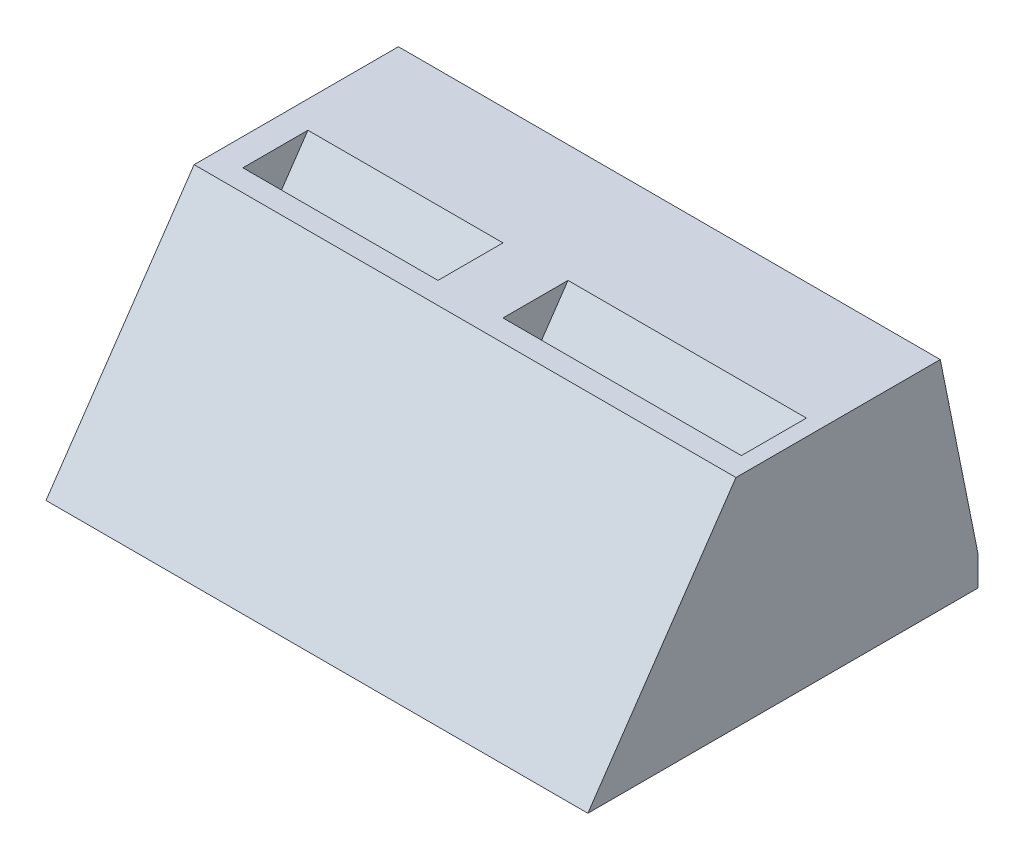
SolidWorks part; units mm, degrees
ref_plane "Ebene vorne" through (0, 0, 0) normal (0, 0, 1) x (1, 0, 0)
ref_plane "Ebene oben" through (0, 0, 0) normal (0, 1, 0) x (1, 0, 0)
ref_plane "Ebene rechts" through (0, 0, 0) normal (1, 0, 0) x (0, 0, -1)
sketch "Skizze1" plane through (0, 0, 0) normal (0, 0, 1) x (1, 0, 0)
  line L1 (-25, -15) -> (25, -15)
  line L2 (-25, -15) -> (-25, 15)
  line L3 (-25, 15) -> (25, 15)
  line L4 (25, -15) -> (25, 15)
  line L5 (-25, -15) -> (25, 15) construction
  line L6 (-25, 15) -> (25, -15) construction
  point P0 (0, 0)
  dimension "D1" = 50
  dimension "D2" = 30
extrude "Aufsatz-Linear austragen1" add sketch "Skizze1" along normal blind 40
ref_plane "Ebene1" through (0, 0, 0) normal (-1, 0, 0) x (0, 0, 1)
sketch "Skizze2" plane through (0, 0, 0) normal (-1, 0, 0) x (0, 0, 1)
  line L0 (7.5, 15) -> (28, -15)
  line L1 (40, 15) -> (0, 15) construction
  line L2 (40, -15) -> (0, -15) construction
  line L3 (28, -15) -> (34, -15)
  line L4 (34, -15) -> (13.5, 15)
  line L5 (13.5, 15) -> (7.5, 15)
  line L6 (40, 15) -> (40, -15) construction
  line L8 (26.6333, -13) -> (32.6333, -13)
  dimension "D1" = 6
  dimension "D2" = 6
  dimension "D3" = 7.5
  dimension "D4" = 2
extrude "FPV_Sender" cut sketch "Skizze2" against normal blind 22 from offset 1.5 contours L0 L8 L4 L5 region at (0, 1, 20.0667) offset against normal yes
sketch "Skizze4" plane through (0, 0, 0) normal (-1, 0, 0) x (0, 0, 1)
  line L0 (13.5, 15) -> (7.5, 15)
  line L1 (7.5, 15) -> (26.6333, -13)
  line L2 (7.5, 15) -> (26.6333, -13) construction
  line L3 (26.6333, -13) -> (32.6333, -13)
  line L4 (32.6333, -13) -> (13.5, 15) construction
  line L5 (32.6333, -13) -> (13.5, 15)
  dimension "D1" = 28
extrude "Empfänger" cut sketch "Skizze4" along normal blind 18 from offset 4.5
sketch "Skizze5" plane through (-25, 0, 0) normal (-1, 0, 0) x (0, 0, 1)
  line L0 (15.5, 15) -> (40, 15)
  line L1 (40, 15) -> (0, 15) construction
  line L2 (40, 15) -> (40, -20.8537)
  line L3 (40, 15) -> (40, -15) construction
  line L4 (40, -20.8537) -> (15.5, 15)
  line L5 (32.6333, -13) -> (13.5, 15) construction
  line L6 (5.5, 15) -> (0, -12.25)
  line L7 (0, 15) -> (0, -15) construction
  line L8 (0, -12.25) -> (0, 15)
  line L9 (0, 15) -> (5.5, 15)
  line L10 (40, -15) -> (0, -15) construction
  dimension "D1" = 2
  dimension "D2" = 2.75
  dimension "D3" = 2
extrude "Schnitt-Linear austragen3" cut sketch "Skizze5" against normal through all and the other way through all
sketch "Skizze7" plane through (25, 0, 0) normal (1, 0, 0) x (0, 0, -1)
  line L0 (-5.5, 15) -> (-15.5, 15)
  line L1 (-15.5, 15) -> (-22.3333, 5)
  line L2 (-15.5, 15) -> (-36, -15) construction
  line L3 (-22.3333, 5) -> (-3.4817, 5)
  line L4 (0, -12.25) -> (-5.5, 15) construction
  line L5 (-3.4817, 5) -> (-5.5, 15)
  dimension "D1" = 10
extrude "Schnitt-Linear austragen5" cut sketch "Skizze7" against normal up to surface (50 mm away) up to face at (-25, 0.55, 11.95)
shell "Wandung2" thickness 2 removed face at (0, -15, 18)
sketch "Skizze6" plane through (0, -13, 0) normal (0, 1, 0) x (1, 0, 0)
  line L0 (23.5, -26.6333) -> (1.5, -26.6333) construction
  line L1 (1.5, -32.6333) -> (8.5, -32.6333)
  line L2 (1.5, -32.6333) -> (1.5, -26.6333)
  line L3 (1.5, -26.6333) -> (8.5, -26.6333)
  line L4 (8.5, -32.6333) -> (8.5, -26.6333)
  dimension "D1" = 7
extrude "Schnitt-Linear austragen4" cut sketch "Skizze6" against normal up to surface (2 mm away) up to face at (0, -15, 18)
sketch "Skizze8" plane through (0, -13, 0) normal (0, 1, 0) x (1, 0, 0)
  line L0 (-22.5, -26.6333) -> (-4.5, -26.6333) construction
  line L1 (-4.5, -32.6333) -> (-8.5, -32.6333)
  line L2 (-4.5, -32.6333) -> (-4.5, -26.6333)
  line L3 (-4.5, -26.6333) -> (-8.5, -26.6333)
  line L4 (-8.5, -32.6333) -> (-8.5, -26.6333)
  dimension "D1" = 4
extrude "Schnitt-Linear austragen7" cut sketch "Skizze8" against normal up to surface (2 mm away) up to face at (5, -15, 29.6333)
